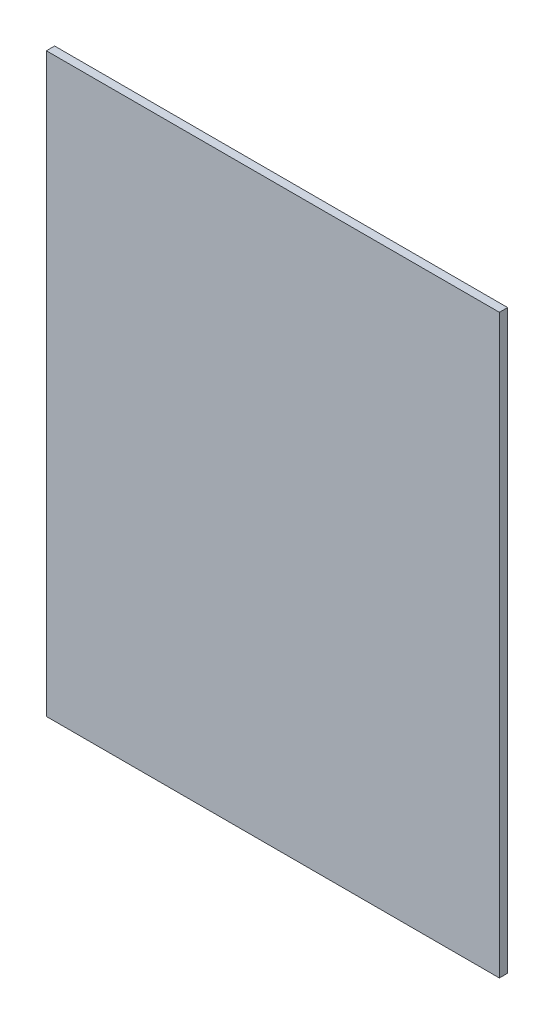
SolidWorks part; units mm, degrees
material "AISI 316 Stainless Steel Sheet (SS)"
ref_plane "Front" through (0, 0, 0) normal (0, 0, 1) x (1, 0, 0)
ref_plane "Top" through (0, 0, 0) normal (0, 1, 0) x (1, 0, 0)
ref_plane "Right" through (0, 0, 0) normal (1, 0, 0) x (0, 0, -1)
sketch "Sketch1" plane through (0, 0, 0) normal (0, 0, 1) x (1, 0, 0)
  line L1 (-55, -70) -> (55, -70)
  line L2 (-55, -70) -> (-55, 70)
  line L3 (-55, 70) -> (55, 70)
  line L4 (55, -70) -> (55, 70)
  line L5 (-55, -70) -> (55, 70) construction
  line L6 (-55, 70) -> (55, -70) construction
  point P0 (0, 0)
  dimension "D1" = 110
  dimension "D2" = 140
extrude "Boss-Extrude1" add sketch "Sketch1" along normal mid plane 2
